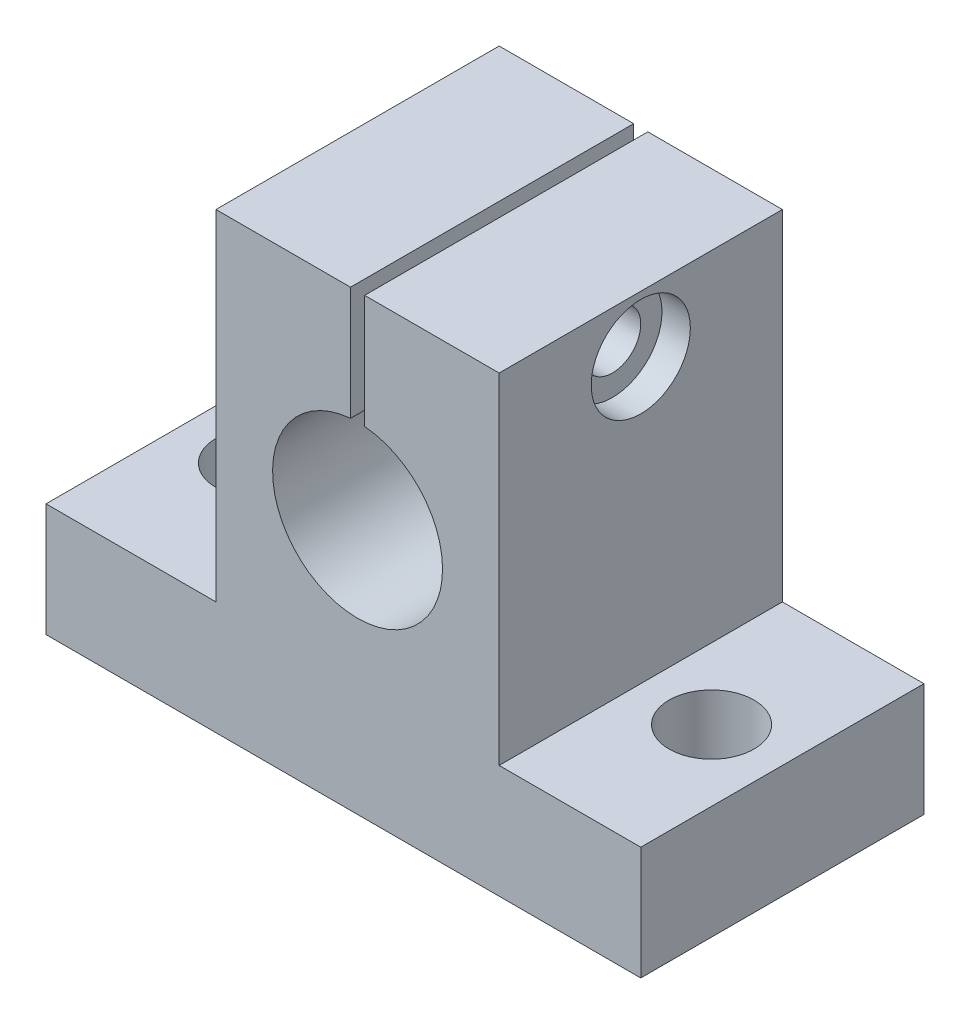
SolidWorks part; units mm, degrees
ref_plane "Спереди" through (0, 0, 0) normal (0, 0, 1) x (1, 0, 0)
ref_plane "Сверху" through (0, 0, 0) normal (0, 1, 0) x (1, 0, 0)
ref_plane "Справа" through (0, 0, 0) normal (1, 0, 0) x (0, 0, -1)
sketch "Эскиз1" plane through (0, 0, 0) normal (0, 0, 1) x (1, 0, 0)
  line L0 (0, 0) -> (0, 18) construction
  line L1 (-22, 0) -> (20, 0)
  line L2 (20, 0) -> (20, 8)
  line L3 (20, 8) -> (10, 8)
  line L4 (10, 8) -> (10, 32)
  line L5 (10, 32) -> (0.5, 32)
  line L6 (0.5, 32) -> (0.5, 23.9791)
  line L7 (-0.5, 23.9791) -> (-0.5, 32)
  line L8 (-0.5, 32) -> (-10, 32)
  line L9 (-10, 32) -> (-10, 8)
  line L10 (-10, 8) -> (-22, 8)
  line L11 (-22, 8) -> (-22, 0)
  arc A0 (-0.5, 23.9791) -> (0.5, 23.9791) centre (0, 18) ccw
  point P16 (0, 0)
  point P17 (0, 0)
  dimension "D1" = 6
  dimension "D2" = 1
  dimension "D3" = 8
  dimension "D4" = 42
  dimension "D5" = 10
  dimension "D6" = 20
  dimension "D7" = 18
  dimension "D8" = 14
  dimension "D9" = 32
extrude "Бобышка-Вытянуть1" add sketch "Эскиз1" along normal blind 20
sketch "Эскиз4" plane through (0, 8, 0) normal (0, 1, 0) x (1, 0, 0)
  line L0 (20, -20) -> (10, -20) construction
  line L1 (-10, -20) -> (-22, -20) construction
  line L2 (20, -20) -> (20, 0) construction
  line L3 (-22, -20) -> (-22, 0) construction
  circle A0 centre (15, -10) radius 3
  circle A1 centre (-17, -10) radius 3
  dimension "D1" = 6
  dimension "D2" = 6
  dimension "D3" = 10
  dimension "D4" = 10
  dimension "D5" = 5
  dimension "D6" = 5
extrude "Вырез-Вытянуть1" cut sketch "Эскиз4" against normal up to surface (8 mm away) up to face at (-1, 0, 10)
sketch "Эскиз5" plane through (10, 0, 0) normal (1, 0, 0) x (0, 0, -1)
  line L0 (-20, 8) -> (-20, 32) construction
  line L1 (-20, 32) -> (0, 32) construction
  circle A0 centre (-10, 28) radius 2
  dimension "D1" = 4
  dimension "D2" = 10
  dimension "D3" = 4
extrude "Вырез-Вытянуть2" cut sketch "Эскиз5" against normal up to surface (20 mm away) up to face at (-10, 20, 10)
sketch "Эскиз6" plane through (10, 0, 0) normal (1, 0, 0) x (0, 0, -1)
  circle A0 centre (-10, 28) radius 3.5
  dimension "D1" = 7
extrude "Вырез-Вытянуть3" cut sketch "Эскиз6" against normal blind 2
sketch "Эскиз7" plane through (-10, 0, 0) normal (-1, 0, 0) x (0, 0, 1)
  line L0 (20, 32) -> (0, 32) construction
  line L1 (14.0415, 28) -> (12.0207, 31.5)
  line L2 (12.0207, 31.5) -> (7.9793, 31.5)
  line L3 (7.9793, 31.5) -> (5.9585, 28)
  line L4 (5.9585, 28) -> (7.9793, 24.5)
  line L5 (7.9793, 24.5) -> (12.0207, 24.5)
  line L6 (12.0207, 24.5) -> (14.0415, 28)
  circle A0 centre (10, 28) radius 3.5 construction
  dimension "D1" = 7
extrude "Вырез-Вытянуть4" cut sketch "Эскиз7" against normal blind 3
